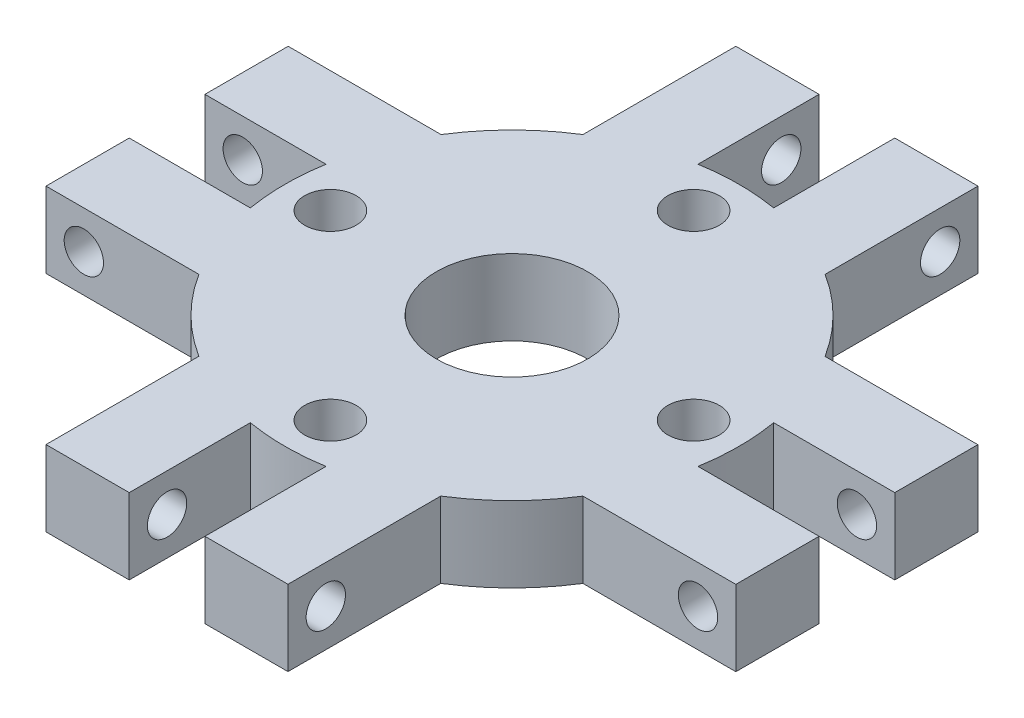
SolidWorks part; units mm, degrees
ref_plane "Front Plane" through (0, 0, 0) normal (0, 0, 1) x (1, 0, 0)
ref_plane "Top Plane" through (0, 0, 0) normal (0, 1, 0) x (1, 0, 0)
ref_plane "Right Plane" through (0, 0, 0) normal (1, 0, 0) x (0, 0, -1)
sketch "Sketch1" plane through (0, 0, 0) normal (0, 1, 0) x (1, 0, 0)
  line L0 (0, 19.05) -> (0, -19.05) construction
  line L1 (10.16, 19.05) -> (-10.16, 19.05) construction
  line L2 (3.175, 19.05) -> (-3.175, 19.05) construction
  line L3 (-3.175, 28.9436) -> (-10.16, 28.9436)
  line L4 (-3.175, 18.7836) -> (-3.175, 28.9436)
  line L5 (-10.16, 28.9436) -> (-10.16, 16.1145)
  line L6 (3.175, 18.7836) -> (3.175, 28.9436)
  line L7 (3.175, 28.9436) -> (10.16, 28.9436)
  line L8 (10.16, 28.9436) -> (10.16, 16.1145)
  line L9 (10.16, -19.05) -> (-10.16, -19.05) construction
  line L10 (3.175, -19.05) -> (-3.175, -19.05) construction
  line L11 (-3.175, -18.7836) -> (-3.175, -28.9436)
  line L12 (3.175, -18.7836) -> (3.175, -28.9436)
  line L13 (-3.175, -28.9436) -> (-10.16, -28.9436)
  line L14 (3.175, -28.9436) -> (10.1443, -28.9436)
  line L15 (-10.16, -28.9436) -> (-10.16, -16.1145)
  line L16 (10.1443, -28.9436) -> (10.1443, -16.1244)
  line L17 (-19.05, 0) -> (19.05, 0) construction
  line L18 (-19.05, 10.16) -> (-19.05, -10.16) construction
  line L19 (-19.05, 3.175) -> (-19.05, -3.175) construction
  line L20 (-18.7836, -3.175) -> (-28.9436, -3.175)
  line L21 (-18.7836, 3.175) -> (-28.9436, 3.175)
  line L22 (-28.9436, 3.175) -> (-28.9436, 10.16)
  line L23 (-28.9436, -3.175) -> (-28.9436, -10.16)
  line L24 (-28.9436, -10.16) -> (-16.1145, -10.16)
  line L25 (-28.9436, 10.16) -> (-16.1145, 10.16)
  line L26 (19.05, 10.16) -> (19.05, -10.16) construction
  line L27 (19.05, -3.175) -> (19.05, 3.175) construction
  line L28 (18.7836, 3.175) -> (28.9436, 3.175)
  line L29 (18.7836, -3.175) -> (28.9436, -3.175)
  line L30 (28.9436, -3.175) -> (28.9436, -10.16)
  line L31 (28.9436, 3.175) -> (28.9436, 10.1466)
  line L32 (28.9436, 10.1466) -> (16.1229, 10.1466)
  line L33 (28.9436, -10.16) -> (16.1145, -10.16)
  circle A0 centre (0, 0) radius 19.05
  point P7 (0, 19.05)
  point P8 (0, 19.05)
  point P10 (0, 19.05)
  point P14 (0, 19.05)
  point P24 (0, -19.05)
  point P26 (0, -19.05)
  point P40 (-19.05, 0)
  point P42 (-19.05, 0)
  point P54 (19.05, 0)
  point P56 (19.05, 0)
extrude "Boss-Extrude1" add sketch "Sketch1" along normal blind 6.35 contours A0 L4 L3 L5 | A0 L8 L7 L6 | A0 L25 L22 L21 | A0 L20 L23 L24 | A0 L15 L13 L11 | A0 L12 L14 L16 | A0 L33 L30 L29 | A0 L28 L31 L32 | A0 region at (-6.8046, 0, -23.3022) region at (6.8046, 0, -23.3022) region at (-23.3022, 0, -6.8046) region at (23.3039, 0, -6.7973) region at (-23.3022, 0, 6.8046) region at (-6.8046, 0, 23.3022) region at (23.3022, 0, 6.8046) region at (6.796, 0, 23.3042)
sketch "Sketch2" plane through (10.16, 0, 0) normal (1, 0, 0) x (0, 0, -1)
  line L0 (28.9436, 3.175) -> (25.7686, 3.175) construction
  line L1 (28.9436, 6.35) -> (28.9436, 0) construction
  circle A0 centre (25.7686, 3.175) radius 1.651
extrude "Cut-Extrude1" cut sketch "Sketch2" against normal blind 23.368
sketch "Sketch3" plane through (0, 0, -10.1466) normal (0, 0, -1) x (-1, 0, 0)
  line L0 (-28.9436, 3.175) -> (-25.7686, 3.175) construction
  line L1 (-28.9436, 6.35) -> (-28.9436, 0) construction
  circle A0 centre (-25.7686, 3.175) radius 1.651
extrude "Cut-Extrude2" cut sketch "Sketch3" against normal blind 23.368
sketch "Sketch4" plane through (10.1443, 0, 0) normal (1, 0, 0) x (0, 0, -1)
  line L0 (-28.9436, 3.175) -> (-25.7686, 3.175) construction
  line L1 (-28.9436, 6.35) -> (-28.9436, 0) construction
  circle A0 centre (-25.7686, 3.175) radius 1.651
extrude "Cut-Extrude3" cut sketch "Sketch4" against normal blind 23.368
sketch "Sketch5" plane through (0, 0, 10.16) normal (0, 0, 1) x (1, 0, 0)
  line L0 (-28.9436, 3.175) -> (-25.7686, 3.175) construction
  line L1 (-28.9436, 6.35) -> (-28.9436, 0) construction
  circle A0 centre (-25.7686, 3.175) radius 1.651
extrude "Cut-Extrude4" cut sketch "Sketch5" against normal blind 23.368
sketch "Sketch6" plane through (0, 6.35, 0) normal (0, 1, 0) x (1, 0, 0)
  circle A0 centre (0, 0) radius 6.35
extrude "Cut-Extrude5" cut sketch "Sketch6" against normal blind 14.3002
sketch "Sketch7" plane through (0, 0, 0) normal (0, -1, 0) x (1, 0, 0)
  circle A0 centre (0, 0) radius 15.24 construction
  circle A1 centre (0, 15.24) radius 2.159
  circle A2 centre (15.24, 0) radius 2.159
  circle A3 centre (0, -15.24) radius 2.159
  circle A4 centre (-15.24, 0) radius 2.159
extrude "Cut-Extrude6" cut sketch "Sketch7" against normal blind 13.462
